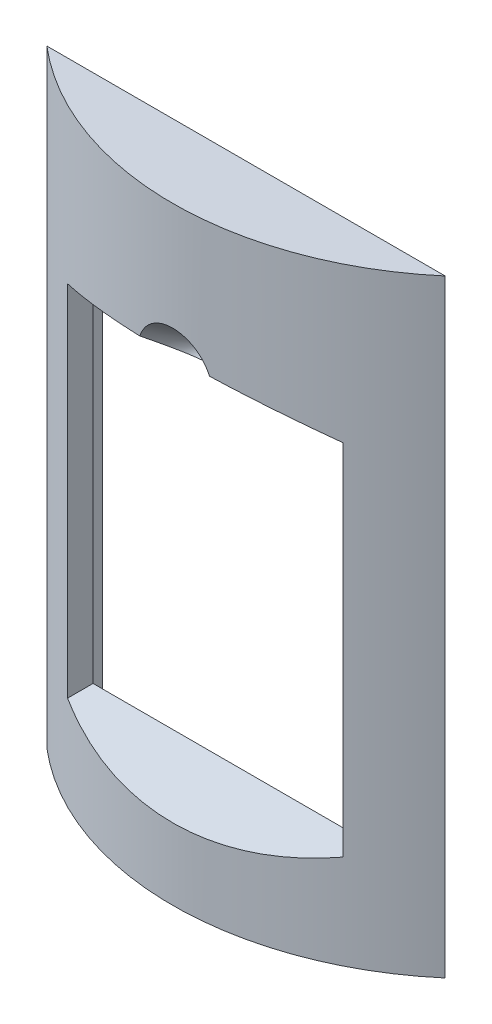
SolidWorks part; units mm, degrees
ref_plane "Front Plane" through (0, 0, 0) normal (0, 0, 1) x (1, 0, 0)
ref_plane "Top Plane" through (0, 0, 0) normal (0, 1, 0) x (1, 0, 0)
ref_plane "Right Plane" through (0, 0, 0) normal (1, 0, 0) x (0, 0, -1)
sketch "Sketch1" plane through (0, 0, 0) normal (0, 1, 0) x (1, 0, 0)
  line L0 (0, 0) -> (-68.5, 0)
  line L1 (0, 0) -> (68.5, 0)
  line L2 (0, 0) -> (0, 7.5) construction
  line L3 (-68.5, 12.3042) -> (-95, 12.3042)
  line L5 (-68.5, 0) -> (-68.5, 7.5)
  line L6 (-68.5, 7.5) -> (68.5, 7.5) construction
  line L7 (68.5, 7.5) -> (68.5, 0)
  line L8 (0, 0) -> (0, -22.6958) construction
  line L9 (-95, -22.6958) -> (95, -22.6958) construction
  line L10 (-68.5, 0) -> (-70.9217, -4.3744) construction
  line L11 (-75.9883, -1.5695) -> (-70.9217, -4.3744) construction
  line L12 (-68.5, 7.5) -> (-68.5, 12.3042)
  line L13 (68.5, 7.5) -> (68.5, 12.3042)
  line L14 (68.5, 12.3042) -> (95, 12.3042)
  arc A0 (-95, 12.3042) -> (95, 12.3042) centre (0, 123.7327) ccw
  dimension "D3" = 35
  dimension "D1" = 137
  dimension "D2" = 7.5
  dimension "D4" = 190
  dimension "D5" = 5
extrude "Boss-Extrude1" add sketch "Sketch1" along normal blind 290
sketch "Sketch3" plane through (0, 0, 0) normal (0, 0, -1) x (-1, 0, 0)
  line L0 (-70, 232.6) -> (-68.5, 290)
  line L1 (-60.65, 50) -> (60.65, 50)
  line L2 (-60.65, 50) -> (-60.65, 211.2)
  line L3 (-60.65, 211.2) -> (60.65, 211.2)
  line L4 (60.65, 50) -> (60.65, 211.2)
  line L5 (-60.65, 50) -> (60.65, 211.2) construction
  line L6 (-60.65, 211.2) -> (60.65, 50) construction
  line L7 (-70, 30.6) -> (70, 30.6)
  line L8 (-70, 30.6) -> (-70, 232.6)
  line L9 (-70, 232.6) -> (70, 232.6)
  line L10 (70, 30.6) -> (70, 232.6)
  line L11 (-70, 30.6) -> (70, 232.6) construction
  line L12 (-70, 232.6) -> (70, 30.6) construction
  line L13 (-68.5, 290) -> (68.5, 290)
  line L14 (68.5, 290) -> (70, 232.6)
  line L15 (-70, 30.6) -> (-68.5, 0)
  line L16 (-68.5, 0) -> (68.5, 0)
  line L17 (68.5, 0) -> (70, 30.6)
  line L18 (-68.5, 0) -> (68.5, 0) construction
  line L20 (-12.5, 0) -> (-12.5, 30.6)
  line L21 (-12.5, 30.6) -> (12.5, 30.6)
  line L22 (12.5, 0) -> (12.5, 30.6)
  circle A0 centre (0, 220) radius 2
  point P0 (0, 130.6)
  point P5 (0, 131.6)
  point P15 (0, 0)
  point P22 (0, 211.2)
  line M7 (-68.5, 0) -> (68.5, 0)
  line M8 (68.5, 0) -> (68.5, 290)
  line M9 (68.5, 290) -> (-68.5, 290)
  line M10 (-68.5, 290) -> (-68.5, 0)
  dimension "D9" = 4
  dimension "D1" = 121.3
  dimension "D2" = 161.2
  dimension "D3" = 140
  dimension "D4" = 202
  dimension "D5" = 19.4
  dimension "D6" = 50
  dimension "D7" = 25
  dimension "D8" = 12.5
  dimension "D10" = 8.8
extrude "Boss-Extrude2" add sketch "Sketch3" along normal up to surface (12.3042 mm away) contours L9 M10 M8 M9 | L20 L7 M7 M10 | L22 L7 M7 M8 region at (0, 261.3, 0) region at (40.5, 15.3, 0) region at (-40.5, 15.3, 0) up to face at (81.75, 145, -12.3042)
extrude "Cut-Extrude1" cut sketch "Sketch3<3>" against normal through all draft 35 contours L1 L4 L3 L2 region at (0, 130.6, 0) draft outward yes
sketch "Sketch3<3>" plane through (0, 0, 0) normal (0, 0, -1) x (-1, 0, 0) same geometry as "Sketch3"
extrude "Cut-Extrude2" cut sketch "Sketch3<5>" against normal through all draft 36 contours A0 region at (0, 220, 0) draft outward yes
sketch "Sketch3<5>" plane through (0, 0, 0) normal (0, 0, -1) x (-1, 0, 0) same geometry as "Sketch3"
fillet "Fillet2" radius 1 1 edges at (-2, 220, 0)
